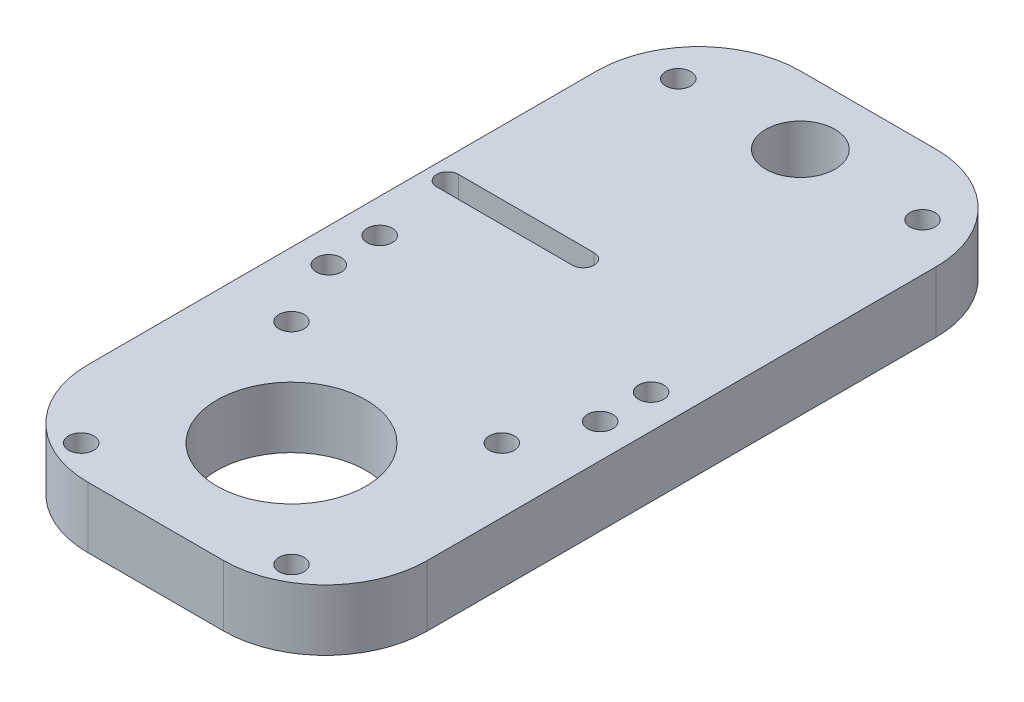
SolidWorks part; units mm, degrees
ref_plane "Front Plane" through (0, 0, 0) normal (0, 0, 1) x (1, 0, 0)
ref_plane "Top Plane" through (0, 0, 0) normal (0, 1, 0) x (1, 0, 0)
ref_plane "Right Plane" through (0, 0, 0) normal (1, 0, 0) x (0, 0, -1)
sketch "Sketch1" plane through (0, 0, 0) normal (0, 1, 0) x (1, 0, 0)
  line L1 (9.489, -12.4157) -> (59.489, -12.4157)
  line L2 (9.489, -12.4157) -> (9.489, 92.5843)
  line L3 (9.489, 92.5843) -> (59.489, 92.5843)
  line L4 (59.489, -12.4157) -> (59.489, 92.5843)
  dimension "D1" = 50
  dimension "D2" = 105
extrude "Boss-Extrude1" add sketch "Sketch1" along normal blind 9
sketch "Sketch2" plane through (0, 9, 0) normal (0, 1, 0) x (1, 0, 0)
  line L0 (9.489, -12.4157) -> (59.489, -12.4157) construction
  line L1 (34.489, 7.5843) -> (34.489, 80.959) construction
  line L6 (59.489, -12.4157) -> (59.489, 92.5843) construction
  line L7 (18.989, 23.0843) -> (18.989, -7.9157) construction
  line L8 (18.989, 23.0843) -> (49.989, -7.9157) construction
  line L9 (49.989, 23.0843) -> (18.989, -7.9157) construction
  line L10 (9.489, 92.5843) -> (9.489, -12.4157) construction
  line L11 (59.489, 40.0843) -> (-5.511, 40.0843) construction
  line L12 (32.489, 52.5843) -> (12.489, 52.5843) construction
  line L13 (32.489, 50.9843) -> (12.489, 50.9843)
  line L14 (32.489, 54.1843) -> (12.489, 54.1843)
  circle A4 centre (34.489, 7.5843) radius 11
  circle A6 centre (49.989, 23.0843) radius 1.85
  circle A7 centre (18.989, -7.9157) radius 1.85
  circle A8 centre (49.989, -7.9157) radius 1.85
  circle A9 centre (18.989, 23.0843) radius 1.85
  circle A12 centre (52.489, 82.5843) radius 1.85
  circle A13 centre (34.489, 82.5843) radius 5.1
  circle A14 centre (16.489, 82.5843) radius 1.85
  arc A15 (32.489, 50.9843) -> (32.489, 54.1843) centre (32.489, 52.5843) ccw
  arc A16 (12.489, 54.1843) -> (12.489, 50.9843) centre (12.489, 52.5843) ccw
  point P9 (22.489, 52.5843)
  dimension "D6" = 22
  dimension "D8" = 3.7
  dimension "D9" = 3.7
  dimension "D10" = 3.7
  dimension "D11" = 3.7
  dimension "D5" = 10.2
  dimension "D7" = 3.7
  dimension "D13" = 3.7
  dimension "D2" = 1.6
  dimension "D3" = 20
  dimension "D12" = 31
  dimension "D31" = 31
  dimension "D4" = 25
  dimension "D14" = 36
  dimension "D15" = 75
  dimension "D17" = 20
  dimension "D18" = 3
  dimension "D16" = 30
extrude "Cut-Extrude1" cut sketch "Sketch2" against normal blind 9
sketch "Sketch3" plane through (0, 9, 0) normal (0, 1, 0) x (1, 0, 0)
  line L0 (9.489, 92.5843) -> (9.489, -12.4157) construction
  line L5 (59.489, -12.4157) -> (59.489, 92.5843) construction
  line L6 (34.489, 18.5843) -> (34.489, 75.7406) construction
  line L7 (9.489, -12.4157) -> (59.489, -12.4157) construction
  circle A0 centre (14.489, 40.5843) radius 1.85
  circle A1 centre (54.489, 40.5843) radius 1.85
  circle A2 centre (54.489, 33.0843) radius 1.85
  circle A3 centre (14.489, 33.0843) radius 1.85
  circle A4 centre (34.489, 7.5843) radius 11 construction
  dimension "D1" = 3.7
  dimension "D2" = 3.7
  dimension "D3" = 3.7
  dimension "D4" = 3.7
  dimension "D5" = 7.5
  dimension "D8" = 5
  dimension "D9" = 5
  dimension "D6" = 53
extrude "Cut-Extrude4" cut sketch "Sketch3" against normal blind 10
fillet "Fillet1" radius 15 4 edges at (59.489, 4.5, 12.4157) (9.489, 4.5, 12.4157) (59.489, 4.5, -92.5843) (9.489, 4.5, -92.5843)
equation "\"D9@Sketch2\"=\"D8@Sketch2\""
equation "\"D10@Sketch2\"=\"D8@Sketch2\""
equation "\"D11@Sketch2\"=\"D8@Sketch2\""
equation "\"D2@Sketch3\"=\"D1@Sketch3\""
equation "\"D3@Sketch3\"=\"D1@Sketch3\""
equation "\"D4@Sketch3\"=\"D1@Sketch3\""
